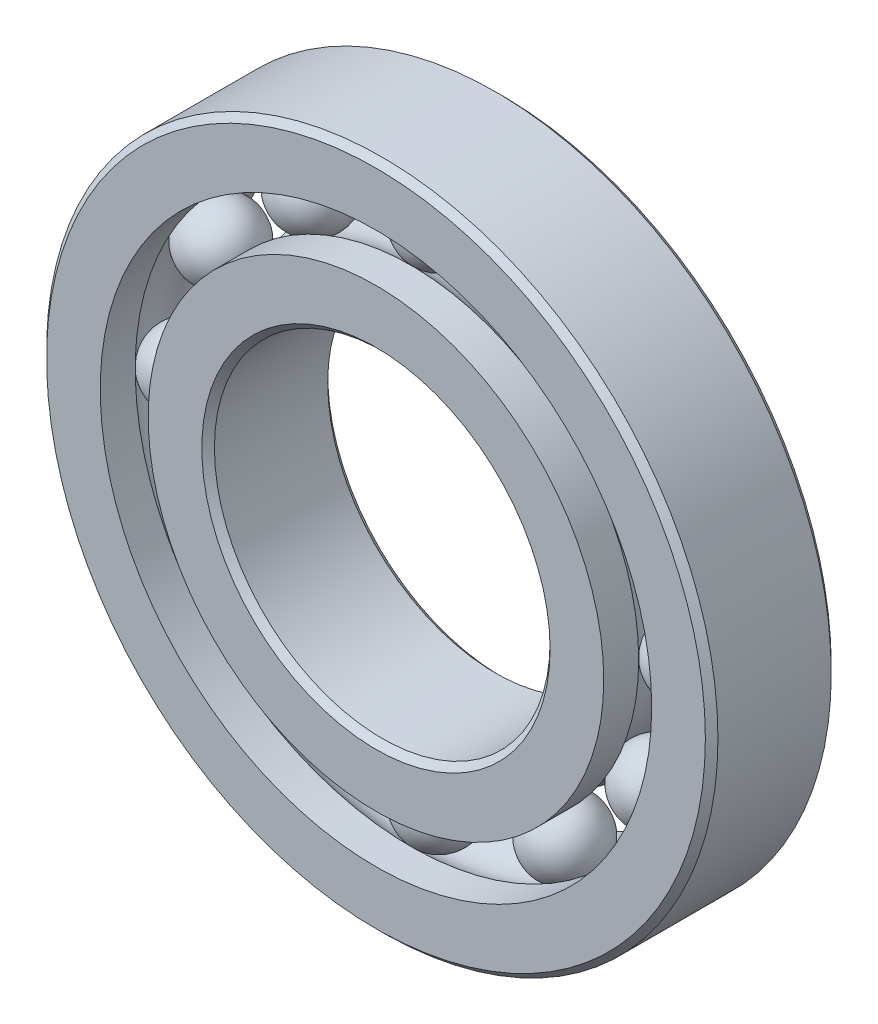
SolidWorks part; units mm, degrees
note: '?' marks a value the reader was unsure of.
ref_plane "Front Plane" through (0, 0, 0) normal (0, 0, 1) x (1, 0, 0)
ref_plane "Top Plane" through (0, 0, 0) normal (0, 1, 0) x (1, 0, 0)
ref_plane "Right Plane" through (0, 0, 0) normal (1, 0, 0) x (0, 0, -1)
sketch "Sketch1" plane through (0, 0, 0) normal (1, 0, 0) x (0, 0, -1)
  line L0 (-4.7625, 0) -> (4.7625, 0) construction
  line L1 (0, 25.4) -> (0, -25.4) construction
  line L2 (4.2863, 25.4) -> (-4.2863, 25.4)
  line L3 (-4.2863, 25.4) -> (-4.7625, 24.9238)
  line L4 (-4.7625, 24.9238) -> (-4.7625, 20.8643)
  line L5 (-4.7625, 20.8643) -> (-2.1167, 20.8643)
  line L6 (4.7625, 20.8643) -> (2.1167, 20.8643)
  line L7 (4.7625, 24.9238) -> (4.7625, 20.8643)
  line L8 (4.2863, 25.4) -> (4.7625, 24.9238)
  line L9 (0, 25.4) -> (0, 19.05) construction
  line L10 (0, 19.05) -> (0, 12.7) construction
  arc A0 (-2.1167, 20.8643) -> (2.1167, 20.8643) centre (0, 19.05) cw
  point P14 (0, 12.7)
  dimension "Width" = 9.525
  dimension "OD" = 50.8
  dimension "D1" = 45
  dimension "D2" = 0.4763
  dimension "Shaft Dia" = 25.4
  dimension "D3" = 4.2333
  dimension "D4" = 1.8143
revolve "Revolve1" add sketch "Sketch1" angle 360 about L0
sketch "Sketch3" plane through (0, 0, 0) normal (1, 0, 0) x (0, 0, -1)
  line L0 (-4.7625, 17.2357) -> (-2.1167, 17.2357)
  line L1 (0, 25.4) -> (0, -25.4) construction
  line L2 (-4.7625, 24.9238) -> (-4.7625, 20.8643) construction
  line L3 (-4.7625, 17.2357) -> (-4.7625, 13.1762)
  line L4 (-4.2863, 25.4) -> (-4.7625, 24.9238) construction
  line L5 (-4.7625, 13.1762) -> (-4.2863, 12.7)
  line L6 (-4.2863, 12.7) -> (4.2862, 12.7)
  line L7 (4.2863, 25.4) -> (4.2863, -25.4) construction
  line L8 (4.2862, 12.7) -> (4.7625, 13.1762)
  line L9 (4.7625, -24.9238) -> (4.7625, 24.9238) construction
  line L10 (4.7625, 13.1762) -> (4.7625, 17.2357)
  line L11 (4.7625, 17.2357) -> (2.1167, 17.2357)
  line L13 (4.2863, 25.4) -> (4.7625, 24.9238) construction
  arc A0 (2.1167, 20.8643) -> (-2.1167, 20.8643) centre (0, 19.05) ccw construction
  arc A1 (2.1167, 17.2357) -> (-2.1167, 17.2357) centre (0, 19.05) cw
revolve "Revolve3" add sketch "Sketch3" angle 360 about L0
sketch "Sketch4" plane through (0, 0, 0) normal (1, 0, 0) x (0, 0, -1)
  line L0 (-2.7878, 19.05) -> (2.7878, 19.05)
  arc A2 (-2.7878, 19.05) -> (2.7878, 19.05) centre (0, 19.05) cw
  arc A3 (2.1167, 20.8643) -> (-2.1167, 20.8643) centre (0, 19.05) ccw construction
revolve "Revolve4" add sketch "Sketch4" angle 360 about L0
ref_axis "Axis1" through (0, 0, -4.7625) along (0, 0, 1)?
pattern_circular "CirPattern1" count 12 every 30 about axis through (0, 0, 0) along (0, 0, 1) of bodies 104
sketch "Sketch5" plane through (0, 0, 0) normal (1, 0, 0) x (0, 0, -1)
  line L0 (-4.7625, 20.8643) -> (-2.1167, 20.8643) construction
  line L1 (-4.5244, 20.8643) -> (-2.7878, 20.8643)
  line L2 (-4.5244, 20.8643) -> (-4.5244, 17.2357)
  line L3 (-4.5244, 17.2357) -> (-2.7878, 17.2357)
  line L4 (-2.7878, 20.8643) -> (-2.7878, 17.2357)
  line L5 (-4.7625, 17.2357) -> (-2.1167, 17.2357) construction
  line L6 (4.7625, 20.8643) -> (2.1167, 20.8643) construction
  line L7 (4.5244, 20.8643) -> (2.7878, 20.8643)
  line L8 (4.5244, 20.8643) -> (4.5244, 17.2357)
  line L9 (4.5244, 17.2357) -> (2.7878, 17.2357)
  line L10 (2.7878, 20.8643) -> (2.7878, 17.2357)
  line L11 (4.7625, 17.2357) -> (2.1167, 17.2357) construction
  line L12 (-4.2863, 25.4) -> (-4.7625, 24.9238) construction
  point P18 (-4.5244, 25.1619)
revolve "Revolve5" [suppressed] add sketch "Sketch5" angle 360 about L0
equation "\"D2@Sketch1\" = \"Width@Sketch1\"*.05"
equation "\"D3@Sketch1\" = \"Width@Sketch1\"/2.25"
equation "\"D4@Sketch1\" = (((\"OD@Sketch1\"-\"Width@Sketch1\")/2)/3.25)/3.5"
equation "\"D2@CirPattern1\" = 360/\"Balls@CirPattern1\""
